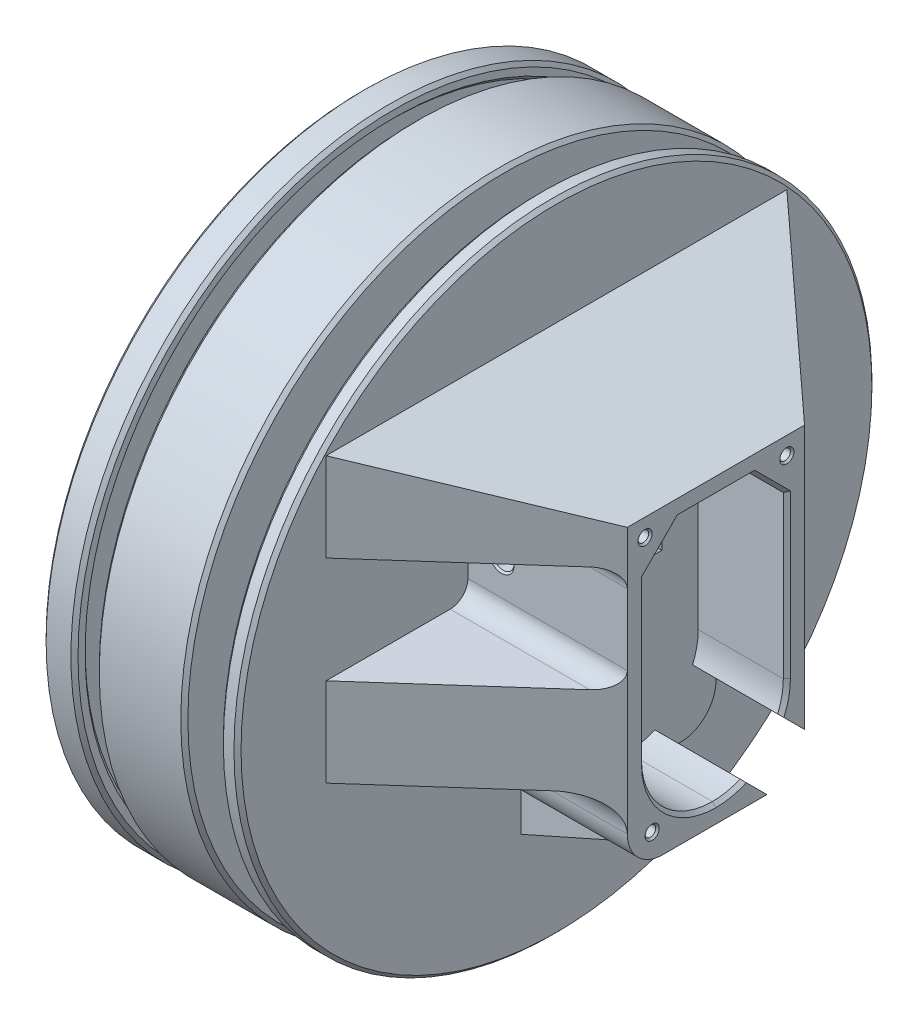
SolidWorks part; units mm, degrees
ref_plane "前视基准面" through (0, 0, 0) normal (0, 0, 1) x (1, 0, 0)
ref_plane "上视基准面" through (0, 0, 0) normal (0, 1, 0) x (1, 0, 0)
ref_plane "右视基准面" through (0, 0, 0) normal (1, 0, 0) x (0, 0, -1)
other "Configuration Table"
sketch "草图1" plane through (0, 0, 0) normal (1, 0, 0) x (0, 0, -1)
  line L1 (-65, 60) -> (65, 60)
  line L2 (-65, 60) -> (-65, -60)
  line L3 (-65, -60) -> (65, -60)
  line L4 (65, 60) -> (65, -60)
  dimension "D1" = 130
  dimension "D2" = 120
  dimension "D3" = 65
  dimension "D4" = 60
extrude "凸台-拉伸1" add sketch "草图1" along normal blind 8
sketch "草图3" plane through (8, 0, 0) normal (1, 0, 0) x (0, 0, -1)
  line L1 (-25, 45) -> (25, 45)
  line L2 (-25, 45) -> (-25, -40)
  line L3 (-25, -40) -> (25, -40)
  line L4 (25, 45) -> (25, -40)
  dimension "D1" = 85
  dimension "D2" = 50
  dimension "D3" = 25
  dimension "D4" = 40
extrude "凸台-拉伸2" add sketch "草图3" along normal blind 20
sketch "草图4" plane through (28, 0, 0) normal (1, 0, 0) x (0, 0, -1)
  line L1 (-8.75, 28) -> (8.75, 28)
  line L2 (-8.75, 28) -> (-8.75, 10.5)
  line L3 (-8.75, 10.5) -> (8.75, 10.5)
  line L4 (8.75, 28) -> (8.75, 10.5)
  dimension "D1" = 17.5
  dimension "D2" = 8.75
  dimension "D3" = 28
extrude "切除-拉伸1" cut sketch "草图4" against normal blind 19
sketch "草图5" plane through (0, 0, -25) normal (0, 0, -1) x (-1, 0, 0)
  line L0 (-8, -60) -> (-8, 60) construction
  circle A0 centre (-17.5, 19.5) radius 3
  dimension "D1" = 6
  dimension "D2" = 9.5
  dimension "D3" = 19.5
extrude "切除-拉伸2" cut sketch "草图5" against normal through all
sketch "草图6" plane through (28, 0, 0) normal (1, 0, 0) x (0, 0, -1)
  line L0 (-20, 40) -> (-20, -35)
  line L1 (-20, -35) -> (20, -35)
  line L2 (20, -35) -> (20, 40)
  line L3 (20, 40) -> (-20, 40)
  line L4 (-25, 45) -> (-25, -40)
  line L5 (-25, -40) -> (25, -40)
  line L6 (25, -40) -> (25, 45)
  line L7 (25, 45) -> (-25, 45)
  line L8 (-25, 45) -> (-25, -40)
  line L9 (-25, -40) -> (25, -40)
  line L10 (25, -40) -> (25, 45)
  line L11 (25, 45) -> (-25, 45)
  dimension "D1" = 0
  dimension "D2" = 5
extrude "凸台-拉伸3" add sketch "草图6" along normal blind 25
chamfer "倒角1" distance 9.5 angle 45 2 edges at (40.5, 40, 20) (40.5, 40, -20)
fillet "圆角1" radius 20 2 edges at (40.5, -35, 20) (40.5, -35, -20)
sketch "草图7" plane through (53, 0, 0) normal (1, 0, 0) x (0, 0, -1)
  line L0 (0, -15) -> (30.2286, -45.2286) construction
  line L1 (0, -15) -> (50000, -15) construction
  line L2 (0, -15) -> (0, 49985) construction
  line L3 (6.0104, -31.617) -> (16.617, -21.0104)
  line L4 (16.617, -21.0104) -> (32.1734, -36.5668)
  line L5 (32.1734, -36.5668) -> (21.5668, -47.1734)
  line L6 (6.0104, -31.617) -> (21.5668, -47.1734)
  point P12 (11.3137, -26.3137)
  point P13 (26.8701, -41.8701)
  dimension "D1" = 45
  dimension "D2" = 22
  dimension "D3" = 16
  dimension "D4" = 7.5
extrude "切除-拉伸3" cut sketch "草图7" against normal up to surface (25 mm away) and the other way through all up to face at (28, 9.6737, 0)
chamfer "倒角2" distance 1 angle 45 4 edges at (28, 19.25, 8.75) (28, 28, 0) (28, 19.25, -8.75) (28, 10.5, 0)
chamfer "倒角3" distance 1 angle 45 8 edges at (53, -34.5993, -3.9832) (53, -29.1421, 14.1421) (53, -18.9832, -19.5993) (53, 7.75, 20) (53, 35.25, 15.25) (53, 40, 0) (53, 35.25, -15.25) (53, 7.75, -20)
sketch "草图8" plane through (0, 45, 0) normal (0, 1, 0) x (1, 0, 0)
  line L0 (53, -25) -> (8, -65)
  line L1 (8, -65) -> (8, -25)
  line L2 (8, -25) -> (53, -25)
  line L3 (0, 0) -> (50000, 0) construction
  line L4 (8, 25) -> (53, 25)
  line L5 (8, 65) -> (8, 25)
  line L6 (53, 25) -> (8, 65)
extrude "凸台-拉伸4" add sketch "草图8" against normal blind 25 from offset 40 offset against normal yes
sketch "草图9" plane through (0, 0, 0) normal (0, 0, 1) x (1, 0, 0)
  line L0 (53, 45) -> (8, 60)
  line L1 (8, 60) -> (8, 45)
  line L2 (8, 45) -> (53, 45)
extrude "凸台-拉伸5" add sketch "草图9" along normal up to surface and the other way up to surface up to face at (30.5, -7.5, 45) other way up to face at (30.5, -7.5, -45)
sketch "草图10" plane through (0, 0, 0) normal (0, 0, 1) x (1, 0, 0)
  line L0 (8, -60) -> (53, -40)
  line L1 (53, -40) -> (8, -40)
  line L2 (8, -40) -> (8, -60)
extrude "凸台-拉伸6" add sketch "草图10" along normal blind 10 and the other way blind 10
fillet "圆角2" radius 10 2 edges at (18, -40, -25) (30.5, -40, 25)
sketch "草图11" plane through (53, 0, 0) normal (1, 0, 0) x (0, 0, -1)
  line L0 (25, 45) -> (-25, 45) construction
  line L1 (-25, 5) -> (-25, -20) construction
  line L2 (25, -20) -> (25, 5) construction
  line L3 (-15, -40) -> (-10, -40) construction
  line L4 (-25, -20) -> (-25, -30) construction
  circle A0 centre (20, 40) radius 1.5
  circle A1 centre (-18, -33) radius 1.5
  circle A2 centre (-20, 40) radius 1.5
  dimension "D1" = 3
  dimension "D2" = 5
  dimension "D3" = 5
  dimension "D4" = 5
  dimension "D5" = 5
  dimension "D6" = 7
  dimension "D7" = 7
extrude "切除-拉伸4" cut sketch "草图11" against normal blind 20 and the other way through all
chamfer "倒角4" distance 0.5 angle 45 3 edges at (53, -33, 16.5) (53, 40, -21.5) (53, 40, 18.5)
sketch "草图13" plane through (0, 0, 0) normal (-1, 0, 0) x (0, 0, 1)
  line L4 (65, -60) -> (65, 60)
  line L5 (65, 60) -> (-65, 60)
  line L6 (-65, 60) -> (-65, -60)
  line L7 (-65, -60) -> (65, -60)
  line L8 (65, -60) -> (65, 60)
  line L9 (65, 60) -> (-65, 60)
  line L10 (-65, 60) -> (-65, -60)
  line L11 (-65, -60) -> (65, -60)
  line L13 (-75, 110) -> (75, 110)
  line L14 (-75, 110) -> (-75, -110)
  line L15 (-75, -110) -> (75, -110)
  line L16 (75, 110) -> (75, -110)
  dimension "D2" = 10
  dimension "D3" = 10
  dimension "D4" = 50
  dimension "D5" = 50
  dimension "D1" = 0
extrude "凸台-拉伸7" add sketch "草图13" against normal blind 8
fillet "圆角4" radius 10 2 edges at (30.5, -20, 25) (30.5, -20, -25)
sketch "草图15" plane through (8, 0, 0) normal (1, 0, 0) x (0, 0, -1)
  line L0 (0, 0) -> (50000, 0) construction
  circle A0 centre (0, 90) radius 2.75
  circle A1 centre (50, 90) radius 2.75
  circle A2 centre (-50, 90) radius 2.75
  circle A3 centre (-50, -90) radius 2.75
  circle A4 centre (50, -90) radius 2.75
  circle A5 centre (0, -90) radius 2.75
  dimension "D1" = 5.5
  dimension "D2" = 50
  dimension "D3" = 50
  dimension "D4" = 90
extrude "切除-拉伸6" cut sketch "草图15" against normal through all
fillet "圆角5" radius 4 4 edges at (4, 110, 75) (4, 110, -75) (4, -110, 75) (4, -110, -75)
sketch "草图16" plane through (0, 45, 0) normal (0, -1, 0) x (1, 0, 0)
  line L3 (8, -65) -> (53, -25)
  line L4 (53, -25) -> (8, -25)
  line L5 (8, -25) -> (8, -65)
  line L6 (8, -65) -> (53, -25)
  line L7 (53, -25) -> (8, -25)
  line L8 (8, -25) -> (8, -65)
  line L9 (8, 65) -> (8, 25)
  line L10 (8, 25) -> (53, 25)
  line L11 (53, 25) -> (8, 65)
  line L12 (8, 65) -> (8, 25)
  line L13 (8, 25) -> (53, 25)
  line L14 (53, 25) -> (8, 65)
  dimension "D1" = 0
  dimension "D2" = 0
extrude "凸台-拉伸8" add sketch "草图16" along normal blind 10
fillet "圆角6" radius 5 4 edges at (30.5, 5, 25) (30.5, 35, 25) (30.5, 5, -25) (30.5, 35, -25)
chamfer "倒角5" distance 0.5 angle 45 2 edges at (17.5, 22.5, -25) (17.5, 22.5, 25)
sketch "草图17" plane through (0, 0, 0) normal (-1, 0, 0) x (0, 0, 1)
  line L4 (75, -106) -> (75, 106)
  line L5 (71, 110) -> (-71, 110)
  line L6 (-75, 106) -> (-75, -106)
  line L7 (-71, -110) -> (71, -110)
  line L8 (75, -106) -> (75, 106)
  line L9 (71, 110) -> (-71, 110)
  line L10 (-75, 106) -> (-75, -106)
  line L11 (-71, -110) -> (71, -110)
  arc A4 (75, 106) -> (71, 110) centre (71, 106) ccw
  arc A5 (-71, 110) -> (-75, 106) centre (-71, 106) ccw
  arc A6 (-75, -106) -> (-71, -110) centre (-71, -106) ccw
  arc A7 (71, -110) -> (75, -106) centre (71, -106) ccw
  arc A8 (75, 106) -> (71, 110) centre (71, 106) ccw
  arc A9 (-71, 110) -> (-75, 106) centre (-71, 106) ccw
  arc A10 (-75, -106) -> (-71, -110) centre (-71, -106) ccw
  arc A11 (71, -110) -> (75, -106) centre (71, -106) ccw
  dimension "D1" = 0
extrude "切除-拉伸7" cut sketch "草图17" against normal blind 8
sketch "草图18" plane through (8, 0, 0) normal (-1, 0, 0) x (0, 0, 1)
  circle A0 centre (0, 0) radius 90
  dimension "D1" = 180
extrude "凸台-拉伸9" add sketch "草图18" along normal blind 5
sketch "草图19" plane through (3, 0, 0) normal (-1, 0, 0) x (0, 0, 1)
  circle A0 centre (0, 0) radius 70
  dimension "D1" = 140
extrude "凸台-拉伸10" add sketch "草图19" along normal blind 10
sketch "草图20" plane through (-7, 0, 0) normal (-1, 0, 0) x (0, 0, 1)
  circle A0 centre (0, 0) radius 90
  dimension "D1" = 180
extrude "凸台-拉伸11" add sketch "草图20" along normal blind 25
sketch "草图24" plane through (-32, 0, 0) normal (-1, 0, 0) x (0, 0, 1)
  circle A0 centre (0, 0) radius 75
  dimension "D1" = 150
extrude "凸台-拉伸14" add sketch "草图24" along normal blind 10
sketch "草图25" plane through (-42, 0, 0) normal (-1, 0, 0) x (0, 0, 1)
  circle A0 centre (0, 0) radius 90
  dimension "D1" = 180
extrude "凸台-拉伸15" add sketch "草图25" along normal blind 5
sketch "草图26" plane through (-42, 0, 0) normal (1, 0, 0) x (0, 0, -1)
  circle A0 centre (0, 0) radius 86
  circle A1 centre (0, 0) radius 90
  circle A2 centre (0, 0) radius 90
  dimension "D1" = 0
  dimension "D2" = 4
extrude "凸台-拉伸16" add sketch "草图26" along normal blind 4
sketch "草图27" plane through (-47, 0, 0) normal (-1, 0, 0) x (0, 0, 1)
  line L0 (0, 0) -> (0, 50000) construction
  line L1 (-40, 60) -> (40, 60) construction
  line L2 (-40, 60) -> (-40, -60) construction
  line L3 (-40, -60) -> (40, -60) construction
  line L4 (40, 60) -> (40, -60) construction
  circle A0 centre (-40, 60) radius 2.75
  circle A1 centre (-40, 0) radius 2.75
  circle A2 centre (-40, -60) radius 2.75
  circle A3 centre (40, -60) radius 2.75
  circle A4 centre (40, 0) radius 2.75
  circle A5 centre (40, 60) radius 2.75
  dimension "D5" = 5.5
  dimension "D1" = 80
  dimension "D2" = 120
  dimension "D3" = 60
  dimension "D4" = 40
extrude "切除-拉伸8" cut sketch "草图27" against normal blind 20
chamfer "倒角6" distance 1 angle 45 6 edges at (-47, -60, 37.25) (-47, 60, 37.25) (-47, 60, -37.25) (-47, 0, -37.25) (-47, 0, 37.25) (-47, -60, -37.25)
chamfer "倒角7" distance 1 angle 45 7 edges at (-38, 0, -86) (-38, 0, -90) (-47, 0, 90) (-7, 0, 90) (-32, 0, 90) (8, 0, 90) (3, 0, 90)
sketch "草图28" plane through (9, 0, 0) normal (1, 0, 0) x (0, 0, -1)
  line L4 (-8.75, 28) -> (-8.75, 10.5)
  line L5 (-8.75, 10.5) -> (8.75, 10.5)
  line L6 (8.75, 10.5) -> (8.75, 28)
  line L7 (8.75, 28) -> (-8.75, 28)
  line L8 (-8.75, 28) -> (-8.75, 10.5)
  line L9 (-8.75, 10.5) -> (8.75, 10.5)
  line L10 (8.75, 10.5) -> (8.75, 28)
  line L11 (8.75, 28) -> (-8.75, 28)
  dimension "D1" = 0
extrude "切除-拉伸9" cut sketch "草图28" against normal blind 0.5
